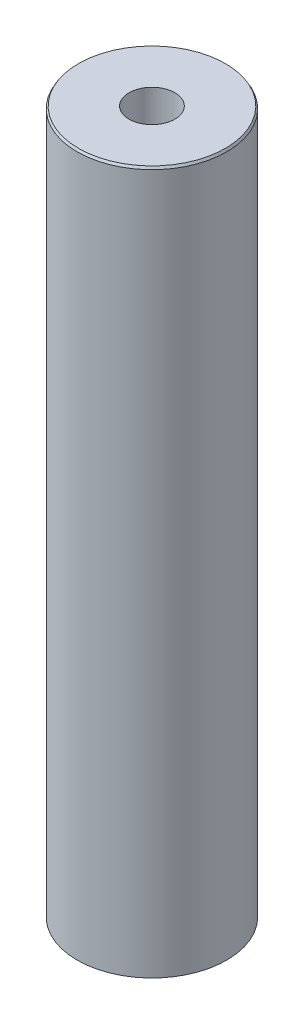
SolidWorks part; units mm, degrees
ref_plane "Front Plane" through (0, 0, 0) normal (0, 0, 1) x (1, 0, 0)
ref_plane "Top Plane" through (0, 0, 0) normal (0, 1, 0) x (1, 0, 0)
ref_plane "Right Plane" through (0, 0, 0) normal (1, 0, 0) x (0, 0, -1)
sketch "Sketch1" plane through (0, 0, 0) normal (0, 1, 0) x (1, 0, 0)
  circle A0 centre (0, 0) radius 55
  dimension "SHAFT_OD" = 110
extrude "Boss-Extrude1" add sketch "Sketch1" along normal blind 517.4798
sketch "Sketch2" plane through (0, 0, 0) normal (0, 1, 0) x (1, 0, 0)
  circle A0 centre (0, 0) radius 16.8533
  dimension "BORE_D" = 33.7066
extrude "Cut-Extrude1" cut sketch "Sketch2" along normal through all
chamfer "Chamfer1" distance 1.7131 angle 30 2 edges at (0, 517.4798, 55) (0, 0, 55) first distance on face at (0, 517.4798, 55) first distance on face at (0, 0, 16.8533)
